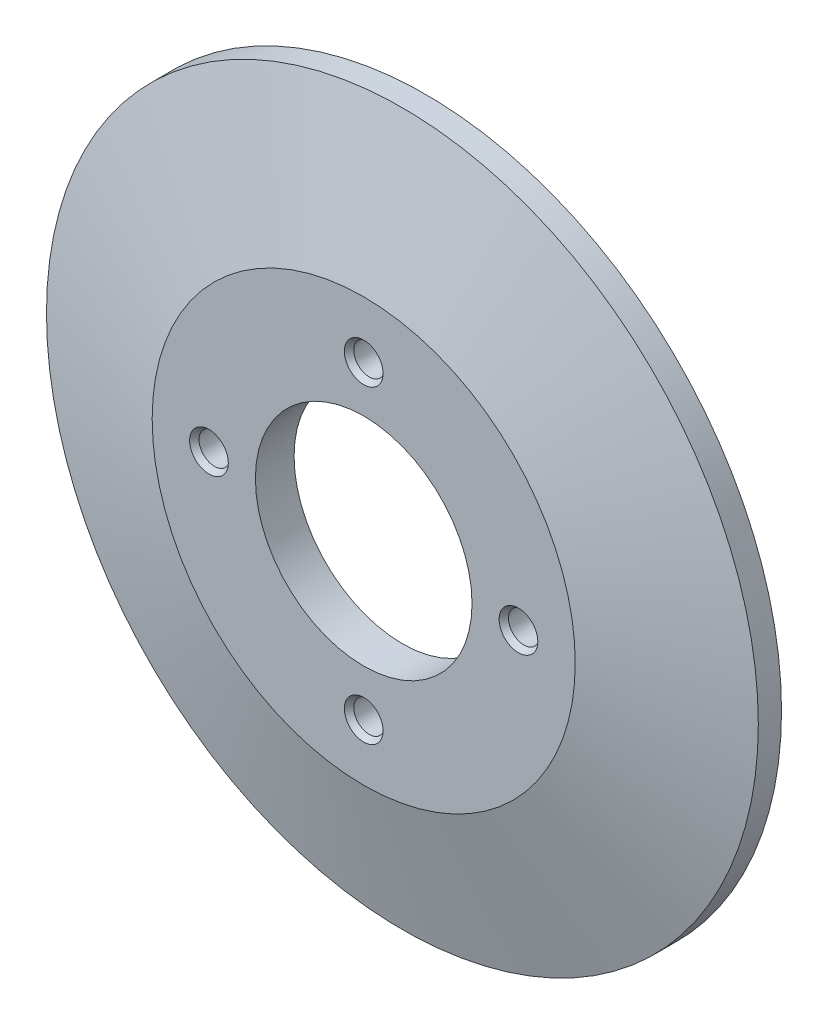
SolidWorks part; units mm, degrees
material "Acier allié inoxydable"
ref_plane "Plan de face" through (0, 0, 0) normal (0, 0, 1) x (1, 0, 0)
ref_plane "Plan de dessus" through (0, 0, 0) normal (0, 1, 0) x (1, 0, 0)
ref_plane "Plan de droite" through (0, 0, 0) normal (1, 0, 0) x (0, 0, -1)
sketch "Esquisse1" plane through (0, 0, 0) normal (0, 0, 1) x (1, 0, 0)
  circle A0 centre (0, 0) radius 46
  dimension "D1" = 92
extrude "Boss.-Extru.1" add sketch "Esquisse1" along normal blind 3
sketch "Esquisse2" plane through (0, 0, 3) normal (0, 0, 1) x (1, 0, 0)
  circle A1 centre (0, 0) radius 46
  circle A2 centre (0, 0) radius 46
  dimension "D1" = 0
extrude "Boss.-Extru.2" add sketch "Esquisse2" along normal blind 5 draft 75
shell "Coque1" thickness 5 removed face at (46, 0, 0)
sketch "Esquisse3" plane through (0, 0, 8) normal (0, 0, 1) x (1, 0, 0)
  circle A0 centre (0, 0) radius 20 construction
  circle A1 centre (0, 20) radius 2
  circle A2 centre (20, 0) radius 2
  circle A3 centre (0, -20) radius 2
  circle A4 centre (-20, 0) radius 2
  point P13 (0, 0)
  dimension "D1" = 40
  dimension "D2" = 4
  dimension "D3" = 4
extrude "Enlèv. mat.-Extru.1" cut sketch "Esquisse3" against normal through all
sketch "Esquisse4" plane through (0, 0, 8) normal (0, 0, 1) x (1, 0, 0)
  circle A0 centre (0, 0) radius 14
  dimension "D1" = 28
extrude "Enlèv. mat.-Extru.2" cut sketch "Esquisse4" against normal through all
chamfer "Chanfrein1" distance 0.5 angle 55 4 edges at (-18, 0, 8) (2, -20, 8) (22, 0, 8) (2, 20, 8) first distance on face at (14, 0, 8)
